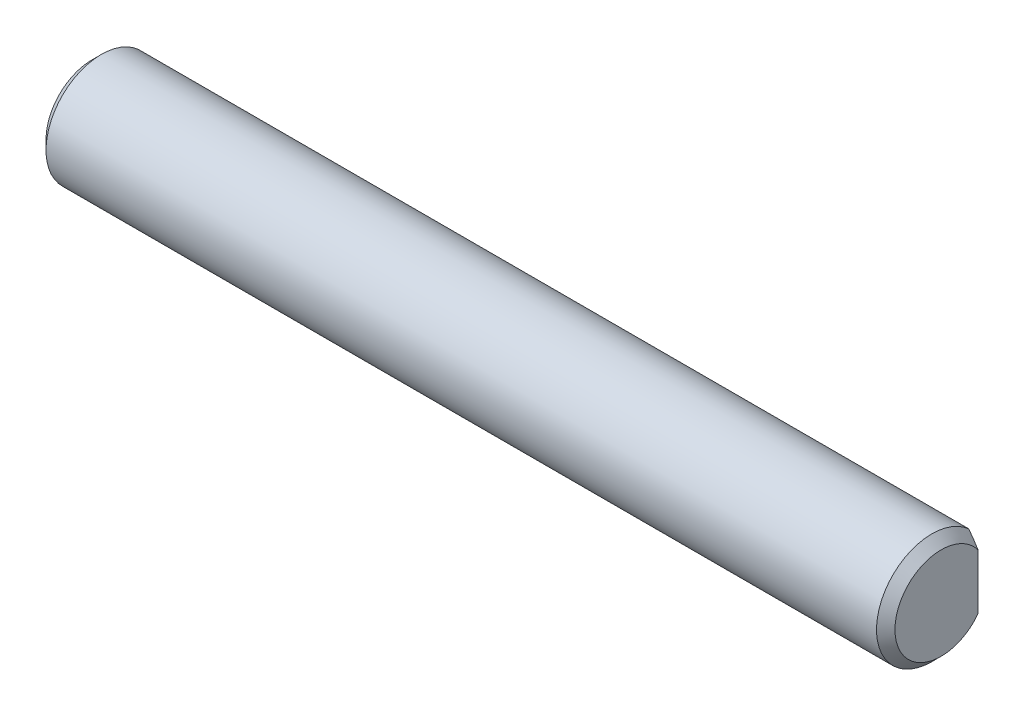
SolidWorks part; units mm, degrees
ref_plane "Front Plane" through (0, 0, 0) normal (0, 0, 1) x (1, 0, 0)
ref_plane "Top Plane" through (0, 0, 0) normal (0, 1, 0) x (1, 0, 0)
ref_plane "Right Plane" through (0, 0, 0) normal (1, 0, 0) x (0, 0, -1)
sketch "Sketch1" plane through (0, 0, 0) normal (1, 0, 0) x (0, 0, -1)
  circle A0 centre (0, 0) radius 3
extrude "Boss-Extrude1" add sketch "Sketch1" along normal blind 46
chamfer "Chamfer1" distance 0.5 angle 45 2 edges at (46, 0, -3) (0, 0, -3)
sketch "Sketch2" plane through (46, 0, 0) normal (1, 0, 0) x (0, 0, -1)
  line L0 (2, 3) -> (2, -3)
  line L4 (3, 3) -> (3, -3)
  line L5 (2, 3) -> (3, 3)
  line L6 (2, -3) -> (3, -3)
  dimension "D1" = 1
extrude "Cut-Extrude1" cut sketch "Sketch2" against normal blind 6
extrude "Cut-Extrude2" cut sketch "Sketch2<3>" along normal blind 6 from offset 46 contours L4 L6 L0 L5 offset against normal yes
sketch "Sketch2<3>" plane through (46, 0, 0) normal (1, 0, 0) x (0, 0, -1) same geometry as "Sketch2"
